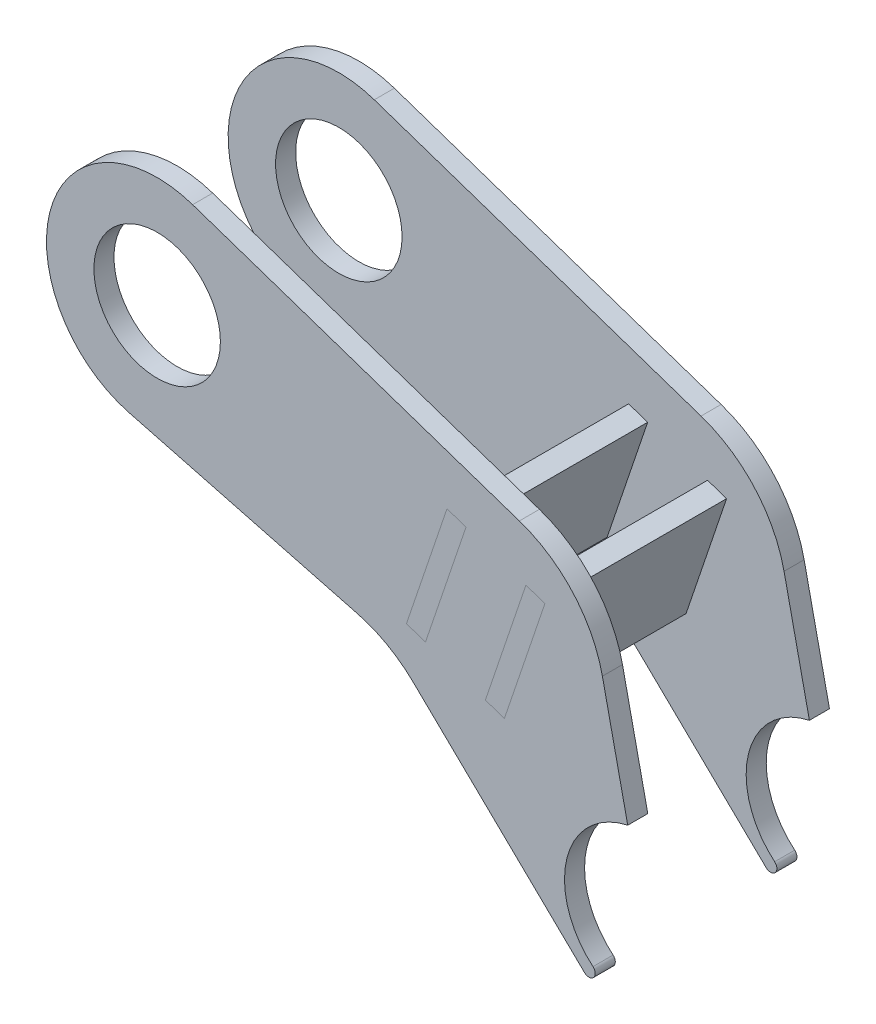
SolidWorks part; units mm, degrees
ref_plane "Front Plane" through (0, 0, 0) normal (0, 0, 1) x (1, 0, 0)
ref_plane "Top Plane" through (0, 0, 0) normal (0, 1, 0) x (1, 0, 0)
ref_plane "Right Plane" through (0, 0, 0) normal (1, 0, 0) x (0, 0, -1)
sketch "Sketch1" plane through (0, 0, 0) normal (0, 0, 1) x (1, 0, 0)
  line L17 (0, 0) -> (44.1306, -14.9292) construction
  line L22 (58.3116, -9.1699) -> (51.9025, -28.1151)
  line L23 (58.3116, -9.1699) -> (61.3192, -10.1873)
  line L28 (51.9025, -28.1151) -> (54.9101, -29.1326)
  line L29 (61.3192, -10.1873) -> (54.9101, -29.1326)
  line L30 (58.3116, -9.1699) -> (54.9101, -29.1326) construction
  line L31 (51.9025, -28.1151) -> (61.3192, -10.1873) construction
  line L32 (45.8314, -4.9479) -> (39.4223, -23.8931)
  line L33 (45.8314, -4.9479) -> (48.839, -5.9653)
  line L34 (39.4223, -23.8931) -> (42.4299, -24.9106)
  line L35 (48.839, -5.9653) -> (42.4299, -24.9106)
  line L36 (45.8314, -4.9479) -> (42.4299, -24.9106) construction
  line L37 (39.4223, -23.8931) -> (48.839, -5.9653) construction
  line L38 (5.608, 16.5771) -> (57.2714, -0.9004)
  line L39 (70.4048, -15.5924) -> (74.4109, -33.9993)
  line L40 (-4.4379, -16.9279) -> (31.6406, -26.3865)
  line L41 (40.4793, -31.3628) -> (67.574, -57.5917)
  line L42 (74.4109, -33.9993) -> (68.2696, -56.8732) construction
  circle A13 centre (0, 0) radius 10
  arc A19 (5.608, 16.5771) -> (-4.4379, -16.9279) centre (0, 0) ccw
  arc A20 (74.4109, -33.9993) -> (68.915, -56.1094) centre (77.1118, -46.4087) ccw
  arc A21 (31.6406, -26.3865) -> (40.4793, -31.3628) centre (26.5686, -45.7327) cw
  arc A22 (57.2714, -0.9004) -> (70.4048, -15.5924) centre (50.8623, -19.8457) cw
  arc A23 (67.574, -57.5917) -> (68.915, -56.1094) centre (68.2696, -56.8732) ccw
  point P9 (56.6108, -19.1512)
  point P12 (44.1306, -14.9292)
  dimension "D1" = 20
  dimension "D2" = 35
  dimension "D5" = 1
  dimension "D7" = 45
  dimension "D12" = 150.621
  dimension "D9" = 20
  dimension "D10" = 4
  dimension "D11" = 10
  dimension "D13" = 239.031
  dimension "D3" = 12.7
  dimension "D4" = 20
  dimension "D6" = 90
  dimension "D8" = 3.175
  dimension "D14" = 23.684
extrude "Boss-Extrude1" add sketch "Sketch1" along normal blind 3.175
ref_plane "Plane1" through (0, 0, -12.775) normal (0, 0, -1) x (-1, 0, 0)
mirror "Mirror3" about plane through (0, 0, -12.775) normal (0, 0, -1) of bodies 101
sketch "Sketch2" plane through (0, 0, 3.175) normal (0, 0, 1) x (1, 0, 0)
  line L13 (45.8314, -4.9479) -> (39.4223, -23.8931)
  line L14 (45.8314, -4.9479) -> (48.839, -5.9653)
  line L15 (39.4223, -23.8931) -> (42.4299, -24.9106)
  line L16 (48.839, -5.9653) -> (42.4299, -24.9106)
  line L17 (51.9025, -28.1151) -> (58.3116, -9.1699)
  line L18 (51.9025, -28.1151) -> (54.9101, -29.1326)
  line L19 (58.3116, -9.1699) -> (61.3192, -10.1873)
  line L20 (54.9101, -29.1326) -> (61.3192, -10.1873)
  line L21 (54.9101, -29.1326) -> (61.3192, -10.1873) construction
  line L22 (42.4299, -24.9106) -> (48.839, -5.9653) construction
ref_plane "Plane2" through (0, 0, -12.775) normal (0, 0, -1) x (-1, 0, 0)
extrude "Boss-Extrude2" add sketch "Sketch2" against normal up to surface (31.9 mm away) separate body up to face at (43.4072, -23.753, -28.725)
